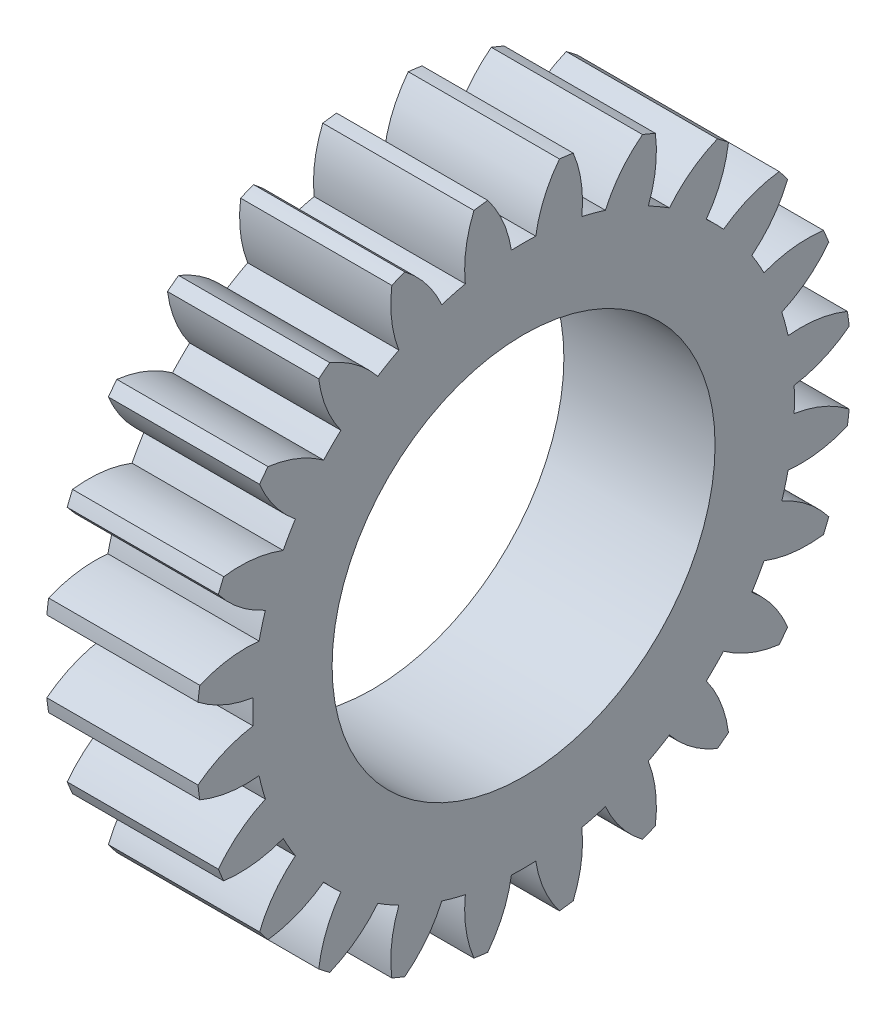
SolidWorks part; units mm, degrees
ref_plane "Plane1" through (0, 0, 0) normal (0, 0, 1) x (1, 0, 0)
ref_plane "Plane2" through (0, 0, 0) normal (0, 1, 0) x (1, 0, 0)
ref_plane "Plane3" through (0, 0, 0) normal (1, 0, 0) x (0, 0, -1)
other "Configuration Table"
sketch "HoldingSke" plane through (0, 0, 0) normal (0, 1, 0) x (1, 0, 0)
  line L0 (0, 0) -> (0.9135, -0.4067)
  line L1 (-15, 0) -> (100, 0) construction
  line L2 (0, 0) -> (-2.1039, 2.3779)
  line L3 (0, 0) -> (-11.863, 4.5341)
  line L4 (0, 0) -> (7.8894, 3.5126)
  line L5 (0, 0) -> (-46.8476, -17.4728)
  line L6 (0, 0) -> (-4.9738, -3.3558)
  line L7 (-2.1039, 2.3779) -> (8.6586, 51.2059)
  line L8 (-76.2, 54.61) -> (-75.5, 54.61)
  line L9 (-71.009, 38.7566) -> (-53.1078, 45.2721)
  line L10 (-76.2, 71.12) -> (104.1128, 71.12)
  line L11 (0, 0) -> (-6, 0)
  line L12 (-76.2, 101.6) -> (-76.162, 101.6)
  line L13 (24.9733, 27.94) -> (52.9518, 28.4284)
  line L14 (24.9733, 27.94) -> (24.9743, 27.94)
  line L15 (24.9733, 27.94) -> (100.4006, 29.5858)
  line L16 (-63.627, -1) -> (-12.827, -1)
  circle A0 centre (0, 0) radius 7.6
  circle A1 centre (0, 0) radius 10.749
  circle A2 centre (0, 0) radius 37.5
  circle A3 centre (0, 0) radius 7.6
  dimension "Num_teeth" = 24
  dimension "Pitch_radius" = 180.3128
  dimension "Width" = 6
  dimension "Thickness" = 6
sketch "BasProSke" plane through (0, 0, 0) normal (0, 1, 0) x (1, 0, 0)
  line L0 (-10, 0) -> (60, 0) construction
  line L1 (0, 0) -> (0, 13)
  line L2 (0, 0) -> (6, 0)
  line L3 (6, 0) -> (6, 13)
  line L4 (6, 13) -> (0, 13)
  dimension "Thickness" = 6
  dimension "Diameter" = 26
revolve "Base-Revolve" add sketch "BasProSke" angle 360 about L0
sketch "TooCutSke" plane through (0, 0, 0) normal (1, 0, 0) x (0, 0, -1)
  line L1 (0, 0) -> (0, 107) construction
  line L2 (0, 0) -> (-0.8513, 11.9698) construction
  line L3 (0, 0) -> (-3.127, 23.752) construction
  line L4 (-0.8513, 11.9698) -> (-1.5635, 11.876) construction
  arc A0 (0.4834, 10.7381) -> (-0.4834, 10.7381) centre (0, 0) ccw
  arc A1 (1.4409, 12.9455) -> (-1.4409, 12.9455) centre (0, 0) ccw
  circle A2 centre (0, 0) radius 12 construction
  circle A3 centre (0, 0) radius 11.2763 construction
  arc A4 (-0.4834, 10.7381) -> (-1.4409, 12.9455) centre (-5.2252, 9.9926) ccw
  arc A5 (1.4409, 12.9455) -> (0.4834, 10.7381) centre (5.2252, 9.9926) ccw
extrude "ToothCut" cut sketch "TooCutSke" along normal through all
fillet "Breaks" [suppressed] radius 0.02 tangent propagation no
fillet "RootFillets" [suppressed] radius 0.251
pattern_circular "TeethCuts" count 24 every 15 about axis through (-10, 0, 0) along (1, 0, 0) of "ToothCut", "RootFillets", "Breaks"
sketch "HubNeaOneSke" plane through (0, 0, 0) normal (-1, 0, 0) x (0, 0, 1)
  circle A0 centre (0, 0) radius 10.749
  dimension "Diameter" = 21.498
extrude "HubNearOne" [suppressed] add sketch "HubNeaOneSke" along normal blind 44.0001
sketch "HubNeaBotSke" plane through (0, 0, 0) normal (-1, 0, 0) x (0, 0, 1)
  circle A0 centre (0, 0) radius 10.749
  dimension "Diameter" = 21.498
extrude "HubNearBoth" [suppressed] add sketch "HubNeaBotSke" along normal blind 22
ref_plane "FarPln" through (6, 0, 0) normal (1, 0, 0) x (0, 0, -1)
sketch "HubFarSke" plane through (6, 0, 0) normal (1, 0, 0) x (0, 0, -1)
  circle A0 centre (0, 0) radius 10.749
  dimension "Diameter" = 21.498
extrude "HubFar" [suppressed] add sketch "HubFarSke" along normal blind 22
sketch "BorSke" plane through (0, 0, 0) normal (1, 0, 0) x (0, 0, -1)
  circle A0 centre (0, 0) radius 7.6
  dimension "Diameter" = 15.2
extrude "Bore" cut sketch "BorSke" along normal mid plane 100.0001
sketch "KeySke" plane through (0, 0, 0) normal (1, 0, 0) x (0, 0, -1)
  line L0 (-0.8, 0) -> (-0.8, 8.3)
  line L1 (-0.8, 8.3) -> (0.8, 8.3)
  line L2 (0.8, 8.3) -> (0.8, 0)
  line L3 (0, 0) -> (0, 34) construction
  line L4 (-0.8, 0) -> (0.8, 0)
  dimension "Width" = 1.6
extrude "Keyway" [suppressed] cut sketch "KeySke" along normal mid plane 100.0001
pattern_circular "Keyway2" [suppressed] count 2 every 90 about axis through (-10, 0, 0) along (1, 0, 0)
equation "' \"Module@HoldingSke\" = 6.35"
equation "' \"Num_teeth@HoldingSke\" = 12"
equation "' \"Ap@HoldingSke\" =  20"
equation "' \"Ap@HoldingSke\" = 20"
equation "' \"Width@HoldingSke\" = 0.5 * 25.4"
equation "' \"Hub_dia@HoldingSke\"= 1 * 25.4"
equation "' \"Hub_dia@HoldingSke\" = 1 * 25.4"
equation "' \"Overall_len@HoldingSke\" = 1.0 * 25.4"
equation "' \"Bore@HoldingSke\" = 0.75 * 25.4"
equation "' \"T_dim@HoldingSke\" = 0.1 * 25.4"
equation "' \"Width@KeySke\" = 0.25 * 25.4"
equation "' \"Show_teeth@HoldingSke\" = 13"
equation "' \"Backlash@HoldingSke\" = 0.009 * 25.4"
equation "' \"Addendum_fac@HoldingSke\" = 1.0"
equation "' \"Dedendum_fac@HoldingSke\" = 1.25"
equation "' \"Dedendum_add@HoldingSke\" = 0.00005 * 25.4"
equation "' \"Clearance_fac@HoldingSke\" = 0.25"
equation "\"Pitch@HoldingSke\" = 1 / \"Module@HoldingSke\""
equation "\"Overcut_dia@TooCutSke\" = (\"Num_teeth@HoldingSke\" + 2 * \"Addendum_fac@HoldingSke\") / \"Pitch@HoldingSke\" + 0.002 * 25.4"
equation "\"Pitch_dia@TooCutSke\" = \"Num_teeth@HoldingSke\" / \"Pitch@HoldingSke\""
equation "\"Base_dia@TooCutSke\" = \"Num_teeth@HoldingSke\" / \"Pitch@HoldingSke\" * cos((\"Ap@HoldingSke\"  * 3.14159265 / 180))"
equation "\"Root_dia@TooCutSke\" = (\"Num_teeth@HoldingSke\" + 2) / \"Pitch@HoldingSke\" - 2 * (\"Addendum_fac@HoldingSke\" + \"Dedendum_fac@HoldingSke\") / \"Pitch@HoldingSke\" - \"Dedendum_add@HoldingSke\" * 2"
equation "\"Half_ang@TooCutSke\" = 180 / \"Num_teeth@HoldingSke\""
equation "\"Half_CT@TooCutSke\" = \"Num_teeth@HoldingSke\" / \"Pitch@HoldingSke\" * sin((3.14159265 / 2 / \"Num_teeth@HoldingSke\")) / 2 - 7 * \"Backlash@HoldingSke\" / 4"
equation "\"Flank_rad@TooCutSke\" = \"Num_teeth@HoldingSke\" / \"Pitch@HoldingSke\" / 5"
equation "\"Radius@RootFillets\" = \"Clearance_fac@HoldingSke\" / \"Pitch@HoldingSke\" + \"Dedendum_add@HoldingSke\""
equation "\"Break_rad@Breaks\" = 0.02 / \"Pitch@HoldingSke\""
equation "\"Thickness@HoldingSke\" = \"Width@HoldingSke\""
equation "\"OAL@HoldingSke\" = \"Thickness@HoldingSke\""
equation "\"MHD@HoldingSke\" = (\"Num_teeth@HoldingSke\" + 2) / \"Pitch@HoldingSke\" - 2 * (\"Addendum_fac@HoldingSke\" + \"Dedendum_fac@HoldingSke\")  / \"Pitch@HoldingSke\" - \"Dedendum_add@HoldingSke\" * 2"
equation "\"MBD@HoldingSke\" = (\"Num_teeth@HoldingSke\" + 2) / \"Pitch@HoldingSke\" - 2 * (\"Addendum_fac@HoldingSke\" + \"Dedendum_fac@HoldingSke\")  / \"Pitch@HoldingSke\" - \"Dedendum_add@HoldingSke\" * 2 - 0.002 * 25.4"
equation "\"MHD@HoldingSke\" = ((sgn( \"MHD@HoldingSke\" - \"Hub_dia@HoldingSke\" )-1)*( \"MHD@HoldingSke\" - \"Hub_dia@HoldingSke\" ))/-2+ \"Hub_dia@HoldingSke\""
equation "\"MBD@HoldingSke\" = ((sgn( \"MBD@HoldingSke\" - \"Bore@HoldingSke\" )-1)*( \"MBD@HoldingSke\" - \"Bore@HoldingSke\" ))/-2+ \"Bore@HoldingSke\""
equation "\"OAL@HoldingSke\" = ((sgn( \"OAL@HoldingSke\" - \"Overall_len@HoldingSke\" )+1)*( \"OAL@HoldingSke\" - \"Overall_len@HoldingSke\" ))/2 + \"Overall_len@HoldingSke\" + 0.000002 * 25.4"
equation "\"Num_teeth@TeethCuts\" = int( \"Show_teeth@HoldingSke\" ) + 1"
equation "\"Num_teeth@TeethCuts\" = ((sgn( \"Num_teeth@TeethCuts\" - \"Num_teeth@HoldingSke\" )-1)*( \"Num_teeth@TeethCuts\" - \"Num_teeth@HoldingSke\" ))/-2+ \"Num_teeth@HoldingSke\""
equation "\"Num_teeth@TeethCuts\" = ((sgn( \"Num_teeth@TeethCuts\" - 2.0)+1)*( \"Num_teeth@TeethCuts\" - 2.0))/2 +2.0"
equation "\"Angle@TeethCuts\" = 360.0 / \"Num_teeth@HoldingSke\""
equation "\"Diameter@BasProSke\" = (\"Num_teeth@HoldingSke\" + 2 * \"Addendum_fac@HoldingSke\") / \"Pitch@HoldingSke\""
equation "\"Thickness@BasProSke\"  = \"Thickness@HoldingSke\""
equation "' \"Fillet_rad@BasProSke\" =  \"Thickness@HoldingSke\" * 0.05"
equation "' \"Fillet_rad@BasProSke\" = \"Thickness@HoldingSke\" * 0.05"
equation "\"MHD@HoldingSke\" = ((sgn( \"MHD@HoldingSke\" - \"Root_dia@TooCutSke\" )-1)*( \"MHD@HoldingSke\" - \"Root_dia@TooCutSke\" ))/-2+ \"Root_dia@TooCutSke\""
equation "\"Diameter@HubNeaOneSke\" = \"MHD@HoldingSke\""
equation "\"Length@HubNearOne\" = \"OAL@HoldingSke\" - \"Thickness@BasProSke\""
equation "\"Diameter@HubNeaBotSke\" = \"MHD@HoldingSke\""
equation "\"Length@HubNearBoth\" = ( \"OAL@HoldingSke\" - \"Thickness@BasProSke\" ) / 2.0"
equation "\"Thickness@FarPln\" = \"Thickness@BasProSke\""
equation "\"Diameter@HubFarSke\" = \"MHD@HoldingSke\""
equation "\"Length@HubFar\" = ( \"OAL@HoldingSke\" - \"Thickness@BasProSke\" ) / 2.0"
equation "\"Diameter@BorSke\" = \"MBD@HoldingSke\""
equation "\"D1@Bore\" = \"OAL@HoldingSke\" * 2.0"
equation "\"D1@Keyway\" = \"OAL@HoldingSke\" * 2.0"
equation "\"Offset@KeySke\" = \"T_dim@HoldingSke\" + \"MBD@HoldingSke\" / 2.0"
